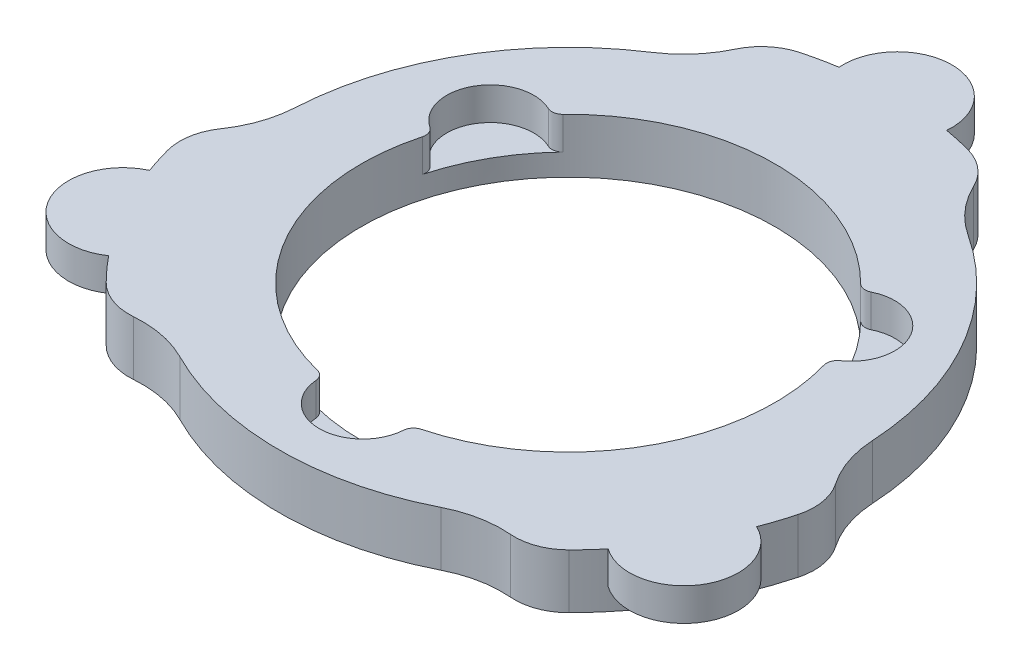
SolidWorks part; units mm, degrees
ref_plane "Спереди" through (0, 0, 0) normal (0, 0, 1) x (1, 0, 0)
ref_plane "Сверху" through (0, 0, 0) normal (0, 1, 0) x (1, 0, 0)
ref_plane "Справа" through (0, 0, 0) normal (1, 0, 0) x (0, 0, -1)
sketch "Sketch1" plane through (0, 0, 0) normal (0, 1, 0) x (1, 0, 0)
  circle A0 centre (0, 0) radius 19
  dimension "D1" = 38
extrude "Boss-Extrude1" add sketch "Sketch1" along normal blind 3.5
sketch "Sketch2" plane through (0, 0, 0) normal (0, 1, 0) x (1, 0, 0)
  circle A0 centre (0, 0) radius 30
  circle A1 centre (0, 0) radius 19
  circle A2 centre (0, 0) radius 25 construction
  circle A3 centre (0, 25) radius 2.8
  circle A4 centre (21.6506, -12.5) radius 2.8
  circle A5 centre (-21.6506, -12.5) radius 2.8
  point P16 (0, 0)
  dimension "D2" = 50
  dimension "D1" = 3
extrude "Boss-Extrude2" add sketch "Sketch2" along normal blind 5
sketch "Sketch4" plane through (0, 0, 0) normal (0, -1, 0) x (1, 0, 0)
  circle A0 centre (-21.6506, 12.5) radius 2.9
  circle A1 centre (21.6506, 12.5) radius 2.9
  circle A2 centre (0, -25) radius 2.9
  point P9 (0, 0)
  dimension "D1" = 3
extrude "Boss-Extrude3" add sketch "Sketch4" along normal blind 2 and the other way blind 5
sketch "Sketch5" plane through (0, 5, 0) normal (0, 1, 0) x (1, 0, 0)
  circle A0 centre (-26.1031, -14.7861) radius 5
  circle A1 centre (0, 0) radius 30 construction
  circle A2 centre (0.2465, 29.999) radius 5
  circle A3 centre (25.8567, -15.2129) radius 5
  point P10 (0, 0)
  dimension "D1" = 3
extrude "Boss-Extrude4" add sketch "Sketch5" against normal blind 3
sketch "Sketch3" plane through (0, 3.5, 0) normal (0, 1, 0) x (1, 0, 0)
  circle A0 centre (0, 0) radius 19
extrude "Cut-Extrude1" cut sketch "Sketch3" against normal blind 10
sketch "Sketch6" plane through (0, 5, 0) normal (0, 1, 0) x (1, 0, 0)
  circle A0 centre (0, 25) radius 3
  circle A1 centre (21.6506, -12.5) radius 2.9
  circle A2 centre (-21.6506, -12.5) radius 2.9
extrude "Cut-Extrude2" [suppressed] cut sketch "Sketch6" against normal blind 3
sketch "Sketch7" plane through (0, 5, 0) normal (0, 1, 0) x (1, 0, 0)
  line L0 (0, 0) -> (-13.774, 37.8437)
  line L1 (0, 0) -> (-43.9393, -7.7477)
  line L2 (-13.774, 37.8437) -> (-43.9393, -7.7477)
  line L3 (39.6606, -6.9932) -> (15.26, 41.9264)
  line L4 (0, 0) -> (15.26, 41.9264)
  line L5 (0, 0) -> (39.6606, -6.9932)
  line L6 (-25.8866, -30.8505) -> (28.6794, -34.1787)
  line L7 (0, 0) -> (28.6794, -34.1787)
  line L8 (0, 0) -> (-25.8866, -30.8505)
  circle A0 centre (0, 0) radius 26.5358
  point P12 (0, 0)
  arc M11 (-23.2848, -18.9161) -> (22.9709, -19.2961) centre (0, 0) ccw
  arc M13 (28.0242, -10.7072) -> (5.2255, 29.5414) centre (0, 0) ccw
  arc M15 (-4.7394, 29.6233) -> (-28.1963, -10.2453) centre (0, 0) ccw
  dimension "D1" = 3
extrude "Cut-Extrude3" cut sketch "Sketch7" against normal blind 13 contours L0 L2 L1 M15 | A0 L0 L1 M15 | L5 L3 L4 M13 | A0 L5 L4 M13 | L8 L6 L7 M11 | A0 L8 L7 M11
fillet "Fillet1" radius 10 6 edges at (-26.1326, 2.5, 4.6079) (-17.0569, 2.5, 20.3276) (17.0569, 2.5, 20.3276) (26.1326, 2.5, 4.6079) (9.0758, 2.5, -24.9355) (-9.0758, 2.5, -24.9355)
fillet "Fillet2" radius 5 6 edges at (-10.2606, 2.5, -28.1908) (-29.5442, 2.5, 5.2094) (-19.2836, 2.5, 22.9813) (19.2836, 2.5, 22.9813) (29.5442, 2.5, 5.2094) (10.2606, 2.5, -28.1908)
sketch "Sketch8" plane through (0, 5, 0) normal (0, 1, 0) x (1, 0, 0)
  circle A0 centre (-16.5249, 9.377) radius 4
  circle A1 centre (0, 0) radius 19
  circle A2 centre (16.3832, 9.6225) radius 4
  circle A3 centre (0.1417, -18.9995) radius 4
  point P12 (0, 0)
  circle M4 centre (0, 0) radius 19
  dimension "D1" = 3
extrude "Cut-Extrude4" cut sketch "Sketch8" along normal blind 3 from offset 3 contours A0 M4 | A1 A2 | A1 A3 offset against normal yes
fillet "Fillet3" radius 1 6 edges at (18.0346, 3.5, -5.9793) (14.0056, 3.5, -12.8392) (-3.8391, 3.5, 18.6081) (4.1163, 3.5, 18.5488) (-14.1956, 3.5, -12.6288) (-18.1218, 3.5, -5.7096)
